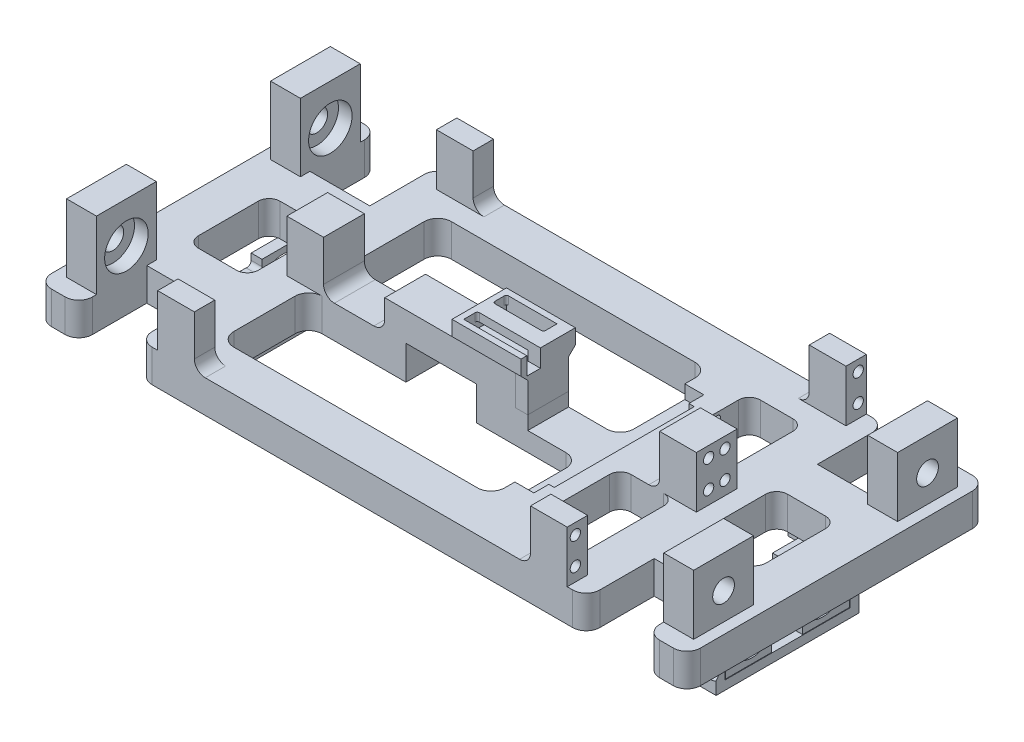
SolidWorks part; units mm, degrees
note: The reader was unsure of these and kept them because the rebuilt part matched: shared geometry of "Sketch42<4>".
other "DogBody"
other "EspHolder"
other "frontCover"
ref_plane "Front Plane" through (0, 0, 0) normal (0, 0, 1) x (1, 0, 0)
ref_plane "Top Plane" through (0, 0, 0) normal (0, 1, 0) x (1, 0, 0)
ref_plane "Right Plane" through (0, 0, 0) normal (1, 0, 0) x (0, 0, -1)
sketch "Sketch1" plane through (0, 0, 0) normal (0, 1, 0) x (1, 0, 0)
  line L0 (-104.3, -55) -> (-104.3, -7.5)
  line L1 (-119.3, -55) -> (-104.3, -55)
  line L2 (-119.3, -55) -> (-119.3, 55)
  line L3 (-119.3, 55) -> (-104.3, 55)
  line L4 (119.3, -55) -> (119.3, 55)
  line L5 (104.3, 55) -> (104.3, 7.5)
  line L6 (-82.3, -55) -> (-82.3, -7.5)
  line L7 (-67.3, -40) -> (-67.3, -7.5)
  line L8 (82.3, -55) -> (82.3, -7.5)
  line L9 (67.3, -40) -> (67.3, -7.5)
  line L10 (-119.3, 0) -> (119.3, 0) construction
  line L11 (-104.3, -7.5) -> (-82.3, -7.5)
  line L12 (-104.3, 7.5) -> (-82.3, 7.5)
  line L15 (-67.3, 40) -> (67.3, 40)
  line L16 (-82.3, 55) -> (82.3, 55)
  line L18 (104.3, 55) -> (119.3, 55)
  line L19 (104.3, -55) -> (119.3, -55)
  line L21 (-82.3, -55) -> (82.3, -55)
  line L22 (-67.3, -40) -> (67.3, -40)
  line L23 (-104.3, 7.5) -> (-104.3, 55)
  line L24 (-82.3, 7.5) -> (-82.3, 55)
  line L25 (-67.3, 7.5) -> (-67.3, 40)
  line L26 (67.3, 7.5) -> (67.3, 40)
  line L27 (82.3, 7.5) -> (82.3, 55)
  line L28 (104.3, -7.5) -> (104.3, -55)
  line L29 (-119.3, 7.5) -> (119.3, 7.5) construction
  line L30 (-119.3, -7.5) -> (119.3, -7.5) construction
  line L31 (82.3, -7.5) -> (104.3, -7.5)
  line L32 (82.3, 7.5) -> (104.3, 7.5)
  line L33 (-67.3, -7.5) -> (67.3, -7.5)
  line L34 (-67.3, 7.5) -> (67.3, 7.5)
  line L35 (-104.3, 55) -> (-82.3, 55) construction
  line L36 (82.3, 55) -> (104.3, 55) construction
  line L37 (82.3, -55) -> (104.3, -55) construction
  line L38 (-82.3, -55) -> (-104.3, -55) construction
  dimension "D1" = 55
  dimension "D2" = 110
  dimension "D3" = 15
  dimension "D4" = 22
  dimension "D5" = 15
  dimension "D6" = 15
  dimension "D7" = 22
  dimension "D8" = 15
  dimension "D11" = 80
  dimension "D12" = 40
  dimension "D13" = 238.6
  dimension "D14" = 119.3
  dimension "D9" = 7.5
  dimension "D10" = 7.5
extrude "Boss-Extrude1" add sketch "Sketch1" along normal blind 12
sketch "Sketch2" plane through (0, 12, 0) normal (0, 1, 0) x (1, 0, 0)
  line L0 (-82.3, 55) -> (-82.3, 7.5) construction
  line L1 (-75.3, 47.5) -> (-63.3, 47.5)
  line L2 (-75.3, 47.5) -> (-75.3, 55)
  line L3 (-75.3, 55) -> (-63.3, 55)
  line L4 (-63.3, 47.5) -> (-63.3, 55)
  line L5 (82.3, 55) -> (-82.3, 55) construction
  line L6 (-75.3, 52) -> (-63.3, 52) construction
  line L7 (-112.3144, 27.5) -> (114.0355, 27.5) construction
  line L8 (0, 0) -> (0, 64.2149) construction
  line L9 (-75.3, 3) -> (-63.3, 3) construction
  line L12 (-75.3, 7.5) -> (-63.3, 7.5)
  line L14 (0, 0) -> (-136.6898, 0) construction
  line L15 (-75.3, -52) -> (-63.3, -52) construction
  line L16 (-75.3, -55) -> (-63.3, -55)
  line L17 (-63.3, -47.5) -> (-63.3, -55)
  line L18 (-75.3, -47.5) -> (-63.3, -47.5)
  line L19 (-75.3, -47.5) -> (-75.3, -55)
  line L20 (-75.3, -3) -> (-63.3, -3) construction
  line L21 (-75.3, -7.5) -> (-63.3, -7.5)
  line L22 (-63.3, -7.5) -> (-63.3, 0)
  line L23 (-63.3, 0) -> (-63.3, 7.5)
  line L24 (-75.3, 7.5) -> (-75.3, 0)
  line L25 (-75.3, 0) -> (-75.3, -7.5)
  line L26 (75.3, -52) -> (63.3, -52) construction
  line L27 (75.3, -47.5) -> (75.3, -55)
  line L28 (75.3, -47.5) -> (63.3, -47.5)
  line L29 (63.3, -47.5) -> (63.3, -55)
  line L30 (75.3, -55) -> (63.3, -55)
  line L31 (75.3, -3) -> (63.3, -3) construction
  line L32 (75.3, 3) -> (63.3, 3) construction
  line L33 (75.3, 7.5) -> (75.3, 0)
  line L34 (75.3, 7.5) -> (63.3, 7.5)
  line L35 (63.3, 0) -> (63.3, 7.5)
  line L36 (63.3, -7.5) -> (63.3, 0)
  line L37 (75.3, -7.5) -> (63.3, -7.5)
  line L38 (75.3, 0) -> (75.3, -7.5)
  line L39 (75.3, 52) -> (63.3, 52) construction
  line L40 (75.3, 55) -> (63.3, 55)
  line L41 (63.3, 47.5) -> (63.3, 55)
  line L42 (75.3, 47.5) -> (63.3, 47.5)
  line L43 (75.3, 47.5) -> (75.3, 55)
  point P29 (-63.3, 0)
  point P32 (-75.3, 0)
  dimension "D1" = 7
  dimension "D2" = 7.5
  dimension "D3" = 12
  dimension "D5" = 24.5
extrude "Boss-Extrude2" add sketch "Sketch2" along normal blind 19
sketch "Sketch3" plane through (-75.3, 0, 0) normal (-1, 0, 0) x (0, 0, 1)
  line L0 (-27.5, -10.7851) -> (-27.5, 36.9377) construction
  line L1 (-47.5, 31) -> (-47.5, 12) construction
  line L2 (-55, 12) -> (55, 12) construction
  line L3 (0, 0) -> (0, 40.8102) construction
  line L4 (-55, 0) -> (55, 0) construction
  circle A0 centre (-52, 17) radius 1.9
  circle A1 centre (-52, 27) radius 1.9
  circle A2 centre (-3, 17) radius 1.9
  circle A3 centre (-3, 27) radius 1.9
  circle A4 centre (3, 27) radius 1.9
  circle A5 centre (3, 17) radius 1.9
  circle A6 centre (52, 17) radius 1.9
  circle A7 centre (52, 27) radius 1.9
  dimension "D3" = 3.8
  dimension "D4" = 3.8
  dimension "D1" = 4.5
  dimension "D2" = 4.5
  dimension "D5" = 10
  dimension "D6" = 5
  dimension "D7" = 24.5
extrude "Cut-Extrude1" cut sketch "Sketch3" against normal through all
sketch "Sketch4" plane through (104.3, 0, 0) normal (-1, 0, 0) x (0, 0, 1)
  line L0 (47.5, 31) -> (47.5, 12) construction
  line L1 (-55, 12) -> (55, 12) construction
  line L2 (-1000, 0) -> (49000, 0) construction
  line L3 (0, -1000) -> (0, 49000) construction
  line L4 (55, 31) -> (55, 12) construction
  line L5 (-48.5, 12) -> (-26.5, 12)
  line L6 (-48.5, 12) -> (-48.5, 34)
  line L7 (-48.5, 34) -> (-26.5, 34)
  line L8 (-26.5, 12) -> (-26.5, 34)
  line L9 (48.5, 12) -> (26.5, 12)
  line L10 (48.5, 12) -> (48.5, 34)
  line L11 (48.5, 34) -> (26.5, 34)
  line L12 (26.5, 12) -> (26.5, 34)
  line L13 (-55, 31) -> (-55, 12) construction
  circle A0 centre (37.5, 22) radius 8
  circle A1 centre (-37.5, 22) radius 8
  dimension "D1" = 16
  dimension "D2" = 10
  dimension "D3" = 10
  dimension "D4" = 22
  dimension "D5" = 22
  dimension "D6" = 22
  dimension "D7" = 22
  dimension "D8" = 6.5
  dimension "D9" = 6.5
extrude "Boss-Extrude3" add sketch "Sketch4" against normal blind 5 separate body
sketch "Sketch6" plane through (109.3, 0, 0) normal (1, 0, 0) x (0, 0, -1)
  line L5 (-48.5, 12) -> (-26.5, 12)
  line L10 (48.5, 12) -> (26.5, 12)
  line L11 (48.5, 12) -> (48.5, 34)
  line L12 (48.5, 34) -> (26.5, 34)
  line L13 (26.5, 12) -> (26.5, 34)
  line L14 (-48.5, 12) -> (-48.5, 34)
  line L15 (-48.5, 34) -> (-26.5, 34)
  line L16 (-26.5, 12) -> (-26.5, 34)
  circle A0 centre (-37.5, 22) radius 4
  circle A1 centre (37.5, 22) radius 4
  dimension "D1" = 8
  dimension "D2" = 8
extrude "Boss-Extrude4" add sketch "Sketch6" along normal blind 6
mirror "Mirror1" about plane through (0, 0, 0) normal (1, 0, 0) of bodies 228 106 107
sketch "Sketch7" plane through (0, 0, 0) normal (0, 1, 0) x (1, 0, 0)
  line L0 (-104.3, 26.5) -> (-104.3, 48.5) construction
  line L1 (-104.3, 30) -> (-82.3, 30)
  line L2 (-104.3, 30) -> (-104.3, 15)
  line L4 (-82.3, 30) -> (-82.3, 15)
  line L5 (-75.3, 47.5) -> (-63.3, 47.5) construction
  line L7 (-104.3, 15) -> (-82.3, 15)
  line L9 (-1000, 0) -> (49000, 0) construction
  line L10 (0, -1000) -> (0, 49000) construction
  line L11 (104.3, 30) -> (104.3, 15)
  line L12 (104.3, 15) -> (82.3, 15)
  line L13 (82.3, 30) -> (82.3, 15)
  line L14 (104.3, 30) -> (82.3, 30)
  line L15 (104.3, -30) -> (82.3, -30)
  line L16 (82.3, -30) -> (82.3, -15)
  line L17 (104.3, -15) -> (82.3, -15)
  line L18 (104.3, -30) -> (104.3, -15)
  line L19 (-104.3, -30) -> (-104.3, -15)
  line L20 (-104.3, -15) -> (-82.3, -15)
  line L21 (-82.3, -30) -> (-82.3, -15)
  line L22 (-104.3, -30) -> (-82.3, -30)
  dimension "D1" = 17.5
  dimension "D2" = 15
  dimension "D3" = 22
extrude "Boss-Extrude5" add sketch "Sketch7" along normal blind 12
sketch "Sketch8" plane through (0, 12, 0) normal (0, 1, 0) x (1, 0, 0)
  line L1 (-104.3, 15) -> (-82.3, 15)
  line L2 (-104.3, 15) -> (-104.3, -15)
  line L3 (-104.3, -15) -> (-82.3, -15)
  line L4 (-82.3, 15) -> (-82.3, -15)
  line L5 (82.3, -15) -> (104.3, -15)
  line L6 (82.3, -15) -> (82.3, 15)
  line L7 (82.3, 15) -> (104.3, 15)
  line L8 (104.3, -15) -> (104.3, 15)
extrude "Cut-Extrude2" cut sketch "Sketch8" against normal through all
sketch "Sketch14" plane through (0, 0, 0) normal (0, 1, 0) x (1, 0, 0)
  line L0 (-67.3, -40) -> (67.3, -40) construction
  line L1 (-7.5, -40) -> (7.5, -40)
  line L2 (-7.5, -40) -> (-7.5, -7.5)
  line L3 (-7.5, 40) -> (7.5, 40)
  line L4 (7.5, -40) -> (7.5, -7.5)
  line L5 (67.3, 40) -> (-67.3, 40) construction
  line L6 (63.3, -7.5) -> (-63.3, -7.5) construction
  line L7 (-63.3, 7.5) -> (63.3, 7.5) construction
  line L8 (7.5, -7.5) -> (-7.5, -7.5)
  line L9 (-7.5, 7.5) -> (7.5, 7.5)
  line L10 (7.5, 7.5) -> (7.5, 40)
  line L11 (-7.5, 7.5) -> (-7.5, 40)
  dimension "D1" = 15
  dimension "D2" = 7.5
extrude "Boss-Extrude8" add sketch "Sketch14" along normal up to surface (12 mm away) up to face at (0, 12, 0)
sketch "Sketch15" plane through (0, 12, 0) normal (0, 1, 0) x (1, 0, 0)
  line L1 (13.3, -31.25) -> (39.3, -31.25)
  line L2 (13.3, -31.25) -> (13.3, 31.25)
  line L4 (39.3, -31.25) -> (39.3, 31.25)
  line L5 (75.3, 47.5) -> (75.3, 55) construction
  line L8 (13.3, 31.25) -> (39.3, 31.25)
  line L9 (-47.3, 14) -> (0.7, 14)
  line L10 (-47.3, 14) -> (-47.3, -14)
  line L11 (-47.3, -14) -> (0.7, -14)
  line L12 (0.7, 14) -> (0.7, -14)
  line L13 (13.3, 27.75) -> (39.3, 27.75) construction
  line L14 (13.3, -27.75) -> (39.3, -27.75) construction
  line L15 (-75.3, 55) -> (-75.3, 47.5) construction
  line L16 (-39.3, -998.765) -> (-39.3, 49001.235) construction
  line L17 (39.3, -1009.0627) -> (39.3, 48990.9373) construction
  point P17 (-75.3, 51.25)
  dimension "D1" = 26
  dimension "D2" = 36
  dimension "D3" = 48
  dimension "D4" = 28
  dimension "D5" = 31.25
  dimension "D6" = 62.5
  dimension "D7" = 55.5
  dimension "D8" = 3.5
  dimension "D9" = 28
  dimension "D10" = 14
  dimension "D11" = 12.6
sketch "Sketch16" plane through (0, 12, 0) normal (0, 1, 0) x (1, 0, 0)
  line L1 (-7.5, 40) -> (7.5, 40)
  line L2 (-7.5, 40) -> (-7.5, 7.5)
  line L3 (-7.5, 7.5) -> (7.5, 7.5)
  line L4 (7.5, 40) -> (7.5, 7.5)
  line L5 (-7.5, -7.5) -> (7.5, -7.5)
  line L6 (-7.5, -7.5) -> (-7.5, -40)
  line L7 (-7.5, -40) -> (7.5, -40)
  line L8 (7.5, -7.5) -> (7.5, -40)
extrude "Cut-Extrude8" cut sketch "Sketch16" against normal through all
sketch "Sketch17" plane through (0, 0, 0) normal (0, 1, 0) x (1, 0, 0)
  line L0 (67.3, 40) -> (-67.3, 40) construction
  line L1 (32.3, 40) -> (47.3, 40)
  line L2 (32.3, 40) -> (32.3, 7.5)
  line L3 (32.3, 7.5) -> (47.3, 7.5)
  line L4 (47.3, 40) -> (47.3, 7.5)
  line L5 (-63.3, 7.5) -> (63.3, 7.5) construction
  line L6 (63.3, -7.5) -> (-63.3, -7.5) construction
  line L7 (32.3, -7.5) -> (47.3, -7.5)
  line L8 (32.3, -7.5) -> (32.3, -40)
  line L9 (32.3, -40) -> (47.3, -40)
  line L10 (47.3, -7.5) -> (47.3, -40)
  line L11 (-67.3, -40) -> (67.3, -40) construction
  line L12 (39.3, -201009.0627) -> (39.3, 248990.9373) construction
  dimension "D1" = 15
  dimension "D2" = 15
  dimension "D3" = 7
  dimension "D4" = 7
extrude "Boss-Extrude9" add sketch "Sketch17" along normal up to surface (12 mm away) up to face at (-93.3, 12, 0)
extrude "Cut-Extrude9" cut sketch "Sketch15" against normal blind 5 contours L8 L2 L1 L4
sketch "Sketch18" plane through (39.3, 0, 0) normal (-1, 0, 0) x (0, 0, 1)
  line L0 (31.25, 7) -> (-31.25, 7) construction
  line L1 (-31.25, 12) -> (-31.25, 7) construction
  line L2 (31.25, 12) -> (31.25, 7) construction
  circle A0 centre (28.25, 9.7) radius 1.2
  circle A1 centre (-28.25, 9.7) radius 1.2
  dimension "D1" = 2.4
  dimension "D2" = 2.4
  dimension "D3" = 2.7
  dimension "D4" = 2.7
  dimension "D5" = 3
  dimension "D6" = 3
extrude "Cut-Extrude10" cut sketch "Sketch18" against normal up to next
sketch "Sketch19" plane through (39.3, 0, 0) normal (-1, 0, 0) x (0, 0, 1)
  line L0 (-31.25, 7) -> (-7.5, 7) construction
  line L1 (-25.75, 7) -> (25.75, 7)
  line L2 (-25.75, 7) -> (-25.75, 14)
  line L3 (-25.75, 14) -> (25.75, 14)
  line L4 (25.75, 7) -> (25.75, 14)
  dimension "D1" = 7
  dimension "D2" = 51.5
  dimension "D3" = 25.75
extrude "Cut-Extrude11" cut sketch "Sketch19" against normal blind 2
sketch "Sketch21" plane through (0, 0, 7.5) normal (0, 0, 1) x (1, 0, 0)
  line L0 (-47.3, 12) -> (0.7, 12) construction
  line L1 (-39.3, 12) -> (2.3491, 12)
  line L2 (-39.3, 12) -> (-39.3, 23)
  line L3 (-39.3, 23) -> (8.7, 23)
  line L5 (13.3, 12) -> (-63.3, 12) construction
  line L7 (8.7, 23) -> (8.7, 12)
  line L8 (2.3491, 12) -> (8.7, 12)
  dimension "D2" = 11
  dimension "D3" = 48
extrude "Boss-Extrude10" add sketch "Sketch21" against normal up to surface (15 mm away) up to face at (63.3, 13.75, -7.5)
sketch "Sketch22" plane through (0, 0, 7.5) normal (0, 0, 1) x (1, 0, 0)
  line L0 (8.7, 12) -> (13.3, 12)
  line L1 (13.3, 12) -> (13.3, 23)
  line L3 (8.7, 23) -> (13.3, 23)
  line L5 (8.7, 23) -> (8.7, 12)
extrude "Boss-Extrude11" add sketch "Sketch22" against normal up to surface (15 mm away) separate body up to face at (63.3, 13.75, -7.5)
sketch "Sketch25" plane through (13.3, 0, 0) normal (1, 0, 0) x (0, 0, -1)
  line L0 (-7.5, 23) -> (7.5, 23)
  line L2 (-7.5, 31) -> (7.5, 31) construction
  line L3 (10, 31) -> (-10, 31)
  line L6 (10, 31) -> (10, 25.5)
  line L7 (7.5, 23) -> (10, 25.5)
  line L8 (-10, 25.5) -> (-10, 31)
  line L9 (-7.5, 23) -> (-10, 25.5)
  dimension "D1" = 20
  dimension "D2" = 10
  dimension "D3" = 5.5
  dimension "D4" = 5.5
extrude "Boss-Extrude12" add sketch "Sketch25" against normal blind 4.6
sketch "Sketch28" plane through (8.7, 0, 0) normal (-1, 0, 0) x (0, 0, 1)
  line L0 (-10, 31) -> (10, 31)
  line L1 (10, 31) -> (10, 25.5)
  line L2 (10, 31) -> (10, 25.5) construction
  line L3 (10, 25.5) -> (7.85, 25.5)
  line L4 (7.85, 25.5) -> (7.85, 28)
  line L5 (7.85, 28) -> (-7.85, 28)
  line L6 (-7.85, 28) -> (-7.85, 25.5)
  line L7 (-7.85, 25.5) -> (-10, 25.5)
  line L8 (-10, 25.5) -> (-10, 31) construction
  line L9 (-10, 25.5) -> (-10, 31)
  dimension "D1" = 15.7
  dimension "D2" = 7.85
  dimension "D3" = 3
  dimension "D4" = 2.5
  dimension "D5" = 2.5
extrude "Boss-Extrude13" add sketch "Sketch28" along normal blind 18.6
sketch "Sketch29" plane through (-9.9, 0, 0) normal (-1, 0, 0) x (0, 0, 1)
  line L1 (-10, 31) -> (10, 31)
  line L2 (-10, 31) -> (-10, 25.5)
  line L3 (-10, 25.5) -> (10, 25.5)
  line L4 (10, 31) -> (10, 25.5)
extrude "Boss-Extrude14" add sketch "Sketch29" along normal blind 2.15
sketch "Sketch31" plane through (0, 28, 0) normal (0, -1, 0) x (1, 0, 0)
  line L0 (13.3, 31.25) -> (13.3, -31.25) construction
  line L1 (7.9, 7.85) -> (4.5, 7.85)
  line L2 (8.7, 7.05) -> (8.7, 3.65) construction
  line L3 (7.9, 2.85) -> (4.5, 2.85)
  line L5 (7.9, 7.85) -> (13.3, 7.85)
  line L6 (7.9, 7.85) -> (7.9, 2.85)
  line L7 (7.9, 2.85) -> (13.3, 2.85)
  line L20 (13.3, 7.85) -> (13.3, 2.85)
  line L21 (7.9, 2.85) -> (13.3, 2.85)
  line L22 (-9.9, -3.65) -> (-9.9, -7.05)
  line L23 (-5.7, -2.85) -> (-9.1, -2.85)
  line L24 (-5.7, -7.85) -> (-9.1, -7.85)
  line L30 (-12.05, 10) -> (-12.05, -10) construction
  line L31 (7.9, -2.85) -> (4.5, -2.85)
  line L32 (-12.05, -10) -> (13.3, -10) construction
  line L33 (8.7, -3.65) -> (8.7, -7.05)
  line L35 (7.9, -7.85) -> (4.5, -7.85)
  line L37 (-5.4657, 7.85) -> (-8.8657, 7.85)
  line L38 (-9.9, 7.05) -> (-9.9, 3.65)
  line L39 (-5.7, 2.85) -> (-9.1, 2.85)
  line L40 (4.5, 7.85) -> (-5.4657, 7.85)
  line L41 (4.5, 2.85) -> (-5.7, 2.85)
  line L42 (4.5, -2.85) -> (-5.7, -2.85)
  line L43 (4.5, -7.85) -> (-5.7, -7.85)
  arc A4 (8.7, 3.65) -> (7.9, 2.85) centre (7.9, 3.65) cw construction
  arc A5 (7.9, 7.85) -> (8.7, 7.05) centre (7.9, 7.05) cw construction
  arc A19 (-9.1, -7.85) -> (-9.9, -7.05) centre (-9.1, -7.05) cw
  arc A21 (-9.1, -2.85) -> (-9.9, -3.65) centre (-9.1, -3.65) ccw
  arc A28 (7.9, -2.85) -> (8.7, -3.65) centre (7.9, -3.65) cw
  arc A29 (7.9, -7.85) -> (8.7, -7.05) centre (7.9, -7.05) ccw
  arc A32 (-8.8657, 7.85) -> (-9.9, 7.05) centre (-9.1008, 7.0853) ccw
  arc A34 (-9.1, 2.85) -> (-9.9, 3.65) centre (-9.1, 3.65) cw
  point P21 (3.7, 2.85)
  point P26 (8.7, 7.85)
  point P29 (3.7, 7.85)
  dimension "D15" = 0.8
  dimension "D16" = 0.8
  dimension "D1" = 5
  dimension "D2" = 5
  dimension "D7" = 2.15
  dimension "D9" = 2.15
  dimension "D11" = 5
  dimension "D13" = 0.8
  dimension "D14" = 3.4
  dimension "D19" = 3.4
  dimension "D20" = 0.8
  dimension "D21" = 3.4
  dimension "D23" = 0.8
extrude "Cut-Extrude12" cut sketch "Sketch31" against normal through all
sketch "Sketch41" plane through (0, 0, 0) normal (0, -1, 0) x (1, 0, 0)
  line L0 (88.3, 21) -> (98.3, 21) construction
  line L1 (88.3, -22.75) -> (98.3, -22.75) construction
  line L2 (88.3, -22.75) -> (88.3, 22.75) construction
  line L3 (88.3, 22.75) -> (98.3, 22.75) construction
  line L4 (98.3, -22.75) -> (98.3, 22.75) construction
  line L5 (88.3, -21) -> (98.3, -21) construction
  line L6 (104.3, -15) -> (104.3, 15) construction
  line L8 (93.3, 22.75) -> (93.3, -22.75) construction
  line L24 (93.3, -22.75) -> (90.3, -22.75)
  line L25 (93.3, -22.75) -> (93.3, 22.75)
  line L26 (93.3, 22.75) -> (90.3, 22.75)
  line L27 (90.3, -22.75) -> (90.3, 22.75)
  line L28 (90.3, 22.75) -> (93.3, 22.75)
  line L29 (90.3, 22.75) -> (90.3, 26.25)
  line L30 (90.3, 26.25) -> (93.3, 26.25)
  line L31 (93.3, 22.75) -> (93.3, 26.25)
  line L32 (90.3, -22.75) -> (93.3, -22.75)
  line L33 (90.3, -22.75) -> (90.3, -26.25)
  line L34 (90.3, -26.25) -> (93.3, -26.25)
  line L35 (93.3, -22.75) -> (93.3, -26.25)
  line M29 (82.3, 15) -> (104.3, 15)
  line M31 (104.3, -15) -> (82.3, -15)
  dimension "D1" = 45.5
  dimension "D2" = 22.75
  dimension "D3" = 42
  dimension "D4" = 21
  dimension "D5" = 10
  dimension "D6" = 6
  dimension "D7" = 3.5
  dimension "D8" = 3.5
  dimension "D9" = 3
extrude "Boss-Extrude18" add sketch "Sketch41" along normal blind 24 separate body contours L26 L31 L30 L29 | L27 L25 L26 M29 | L27 L25 M31 M29 | L27 L24 L25 M31 | L35 L24 L33 L34
sketch "Sketch42" plane through (93.3, 0, 0) normal (1, 0, 0) x (0, 0, -1)
  line L1 (-26.25, 0) -> (26.25, 0)
  line L2 (-26.25, 0) -> (-26.25, -24)
  line L3 (-26.25, -24) -> (26.25, -24)
  line L4 (26.25, 0) -> (26.25, -24)
  line L5 (-22.95, 0) -> (22.95, 0)
  line L6 (-22.95, 0) -> (-22.95, -20.7)
  line L7 (-22.95, -20.7) -> (22.95, -20.7)
  line L8 (22.95, 0) -> (22.95, -20.7)
  line L9 (-5.5, -5.0608) -> (5.5, -5.0608) construction
  line L10 (-5.5, -5.0608) -> (-5.5, 3.3558) construction
  line L11 (-5.5, 3.3558) -> (5.5, 3.3558) construction
  line L12 (5.5, -5.0608) -> (5.5, 3.3558) construction
  line L13 (-5.5, -3.3) -> (-19.95, -3.3)
  line L14 (-5.5, -3.3) -> (-5.5, 0)
  line L15 (-5.5, 0) -> (-19.95, 0)
  line L16 (-19.95, -3.3) -> (-19.95, 0)
  line L17 (5.5, -3.3) -> (19.95, -3.3)
  line L18 (5.5, -3.3) -> (5.5, 0)
  line L19 (5.5, 0) -> (19.95, 0)
  line L20 (19.95, -3.3) -> (19.95, 0)
  line L21 (5.5, -3.5) -> (-5.5, -3.5)
  line L22 (5.5, -3.5) -> (5.5, 0)
  line L23 (5.5, 0) -> (-5.5, 0)
  line L24 (-5.5, -3.5) -> (-5.5, 0)
  line M8 (26.25, 0) -> (-26.25, 0)
  line M9 (-26.25, 0) -> (-26.25, -24)
  line M10 (-26.25, -24) -> (26.25, -24)
  line M11 (26.25, -24) -> (26.25, 0)
  dimension "D1" = 3.3
  dimension "D2" = 3.3
  dimension "D3" = 3.3
  dimension "D4" = 11
  dimension "D5" = 5.5
  dimension "D6" = 3.3
  dimension "D7" = 3.3
  dimension "D8" = 3
  dimension "D9" = 3
  dimension "D10" = 3.5
extrude "Boss-Extrude19" add sketch "Sketch42" along normal blind 8 contours L8 L7 L6 M8 M9 M10 M11
sketch "Sketch43" plane through (93.3, 0, 0) normal (1, 0, 0) x (0, 0, -1)
  line L0 (-55, 0) -> (55, 0) construction
  line L1 (-21.25, -1.5) -> (21.25, -1.5) construction
  line L2 (-21.25, -1.5) -> (-21.25, -19) construction
  line L3 (-21.25, -19) -> (21.25, -19) construction
  line L4 (21.25, -1.5) -> (21.25, -19) construction
  line L5 (-22.95, 0) -> (-22.95, -20.7) construction
  line L7 (22.95, 0) -> (22.95, -20.7) construction
  line L9 (-22.95, -20.7) -> (22.95, -20.7) construction
  circle A1 centre (-21.25, -1.5) radius 0.9
  circle A2 centre (-21.25, -19) radius 0.9
  circle A3 centre (21.25, -1.5) radius 0.9
  circle A4 centre (21.25, -19) radius 0.9
  dimension "D5" = 1.8
  dimension "D6" = 1.8
  dimension "D7" = 1.8
  dimension "D8" = 1.8
  dimension "D1" = 1.5
  dimension "D2" = 1.7
  dimension "D3" = 1.7
  dimension "D4" = 1.7
sketch "Sketch44" plane through (90.3, 0, 0) normal (-1, 0, 0) x (0, 0, 1)
  line L0 (-26.25, 0) -> (26.25, 0) construction
  line L1 (-26.25, 0) -> (-18.75, 0)
  line L2 (-26.25, 0) -> (-26.25, -5)
  line L3 (-26.25, -5) -> (-18.75, -5)
  line L4 (-18.75, 0) -> (-18.75, -5)
  line L6 (26.25, 0) -> (18.75, 0)
  line L7 (26.25, 0) -> (26.25, -5)
  line L8 (26.25, -5) -> (18.75, -5)
  line L9 (18.75, 0) -> (18.75, -5)
  dimension "D1" = 7.5
  dimension "D2" = 7.5
  dimension "D3" = 5
  dimension "D4" = 5
  dimension "D5" = 18.75
  dimension "D6" = 18.75
extrude "Boss-Extrude20" add sketch "Sketch44" along normal blind 7.5
sketch "Sketch45" plane through (0, -5, 0) normal (0, -1, 0) x (1, 0, 0)
  line L0 (82.8, -26.25) -> (82.8, -18.75) construction
  line L1 (82.8, -26.25) -> (90.3, -26.25) construction
  line L2 (82.8, 18.75) -> (82.8, 26.25) construction
  line L3 (82.8, 26.25) -> (90.3, 26.25) construction
  circle A0 centre (86.55, 22.5) radius 2.75
  circle A1 centre (86.55, -22.5) radius 2.75
  dimension "D3" = 5.5
  dimension "D4" = 5.5
  dimension "D1" = 3.75
  dimension "D2" = 3.75
  dimension "D5" = 3.75
  dimension "D6" = 3.75
extrude "Cut-Extrude20" cut sketch "Sketch45" against normal blind 3
sketch "Sketch47" plane through (0, -2, 0) normal (0, -1, 0) x (1, 0, 0)
  circle A3 centre (86.55, -22.5) radius 1.4
  circle A4 centre (86.55, 22.5) radius 1.4
  dimension "D1" = 2.8
  dimension "D2" = 2.8
extrude "Cut-Extrude22" cut sketch "Sketch47" against normal blind 10
sketch "Sketch48" plane through (93.3, 0, 0) normal (1, 0, 0) x (0, 0, -1)
  line L0 (-13, -10.5) -> (13, -10.5) construction
  line L1 (-5, -2.5) -> (-5, -0.2)
  line L2 (-22.95, -20.7) -> (22.95, -20.7) construction
  line L3 (-5.95, -17.7) -> (-5.95, -20.5)
  line L4 (-3.75, -17.7) -> (3.35, -17.7) construction
  line L5 (-3.75, -15.5) -> (3.35, -15.5)
  line L7 (5.55, -17.7) -> (5.55, -20.5)
  line L8 (-22.95, -20.7) -> (22.95, -20.7) construction
  line L9 (-3.5, -2.5) -> (3.8789, -2.5486) construction
  line L11 (-3.5, -4) -> (3.5, -4)
  line L12 (-55, 0) -> (55, 0) construction
  line L13 (-22.95, 0) -> (-22.95, -20.7) construction
  line L14 (-22.75, -20.5) -> (-5.95, -20.5)
  line L15 (-22.75, -20.5) -> (-22.75, -0.2)
  line L16 (-22.75, -0.2) -> (-5, -0.2)
  line L17 (22.75, -20.5) -> (22.75, -0.2)
  line L18 (22.95, 0) -> (22.95, -20.7) construction
  line L19 (5.55, -20.5) -> (22.75, -20.5)
  line L20 (5.3789, -2.5486) -> (5.3789, -0.2)
  line L21 (5.3789, -0.2) -> (22.75, -0.2)
  circle A0 centre (-13, -10.5) radius 8.1
  circle A1 centre (13, -10.5) radius 8.1
  arc A2 (-3.75, -15.5) -> (-5.95, -17.7) centre (-3.75, -17.7) ccw
  arc A3 (5.55, -17.7) -> (3.35, -15.5) centre (3.35, -17.7) ccw
  arc A5 (-5, -2.5) -> (-3.5, -4) centre (-3.5, -2.5) ccw
  arc A6 (3.5, -4) -> (5.3789, -2.5486) centre (3.8789, -2.5486) ccw
  point P13 (0, -17.7)
  point P23 (0, -2.5)
  point P29 (-4.5607, -3.5607)
  dimension "D1" = 16.2
  dimension "D2" = 16.2
  dimension "D6" = 2.2
  dimension "D7" = 11.5
  dimension "D10" = 1.5
  dimension "D12" = 5
  dimension "D8" = 2.2
  dimension "D3" = 26
  dimension "D4" = 13
  dimension "D5" = 10.2
  dimension "D11" = 10
  dimension "D14" = 0.2
  dimension "D15" = 0.2
  dimension "D16" = 0.2
  dimension "D17" = 0.2
extrude "Boss-Extrude22" add sketch "Sketch48" along normal blind 4 from offset 5 separate body
sketch "Sketch50" plane through (0, 0, 0) normal (0, -1, 0) x (1, 0, 0)
  line L0 (-29, -5.5) -> (-8, -5.5) construction
  line L1 (-31.5, -8) -> (-5.5, -8)
  line L2 (-31.5, -8) -> (-31.5, 8)
  line L3 (-31.5, 8) -> (-5.5, 8)
  line L4 (-5.5, -8) -> (-5.5, 8)
  line L6 (-31.5, 8) -> (-5.5, 8) construction
  line L7 (-31.5, 8) -> (-31.5, 5.3) construction
  line L8 (-31.5, 5.3) -> (-5.5, 5.3)
  line L9 (-5.5, 8) -> (-5.5, 5.3) construction
  circle A0 centre (-29, -5.5) radius 1.5 construction
  circle A1 centre (-8, -5.5) radius 1.5 construction
  line M16 (32.3, 7.5) -> (-67.3, 7.5)
  line M22 (-67.3, -7.5) -> (32.3, -7.5)
  dimension "D4" = 3
  dimension "D5" = 3
  dimension "D1" = 16
  dimension "D2" = 26
  dimension "D3" = 8
  dimension "D6" = 2.5
  dimension "D7" = 2.5
  dimension "D8" = 2.5
  dimension "D9" = 2.7
  dimension "D10" = 5.5
extrude "Cut-Extrude23" cut sketch "Sketch50" against normal blind 11 contours L2 L8 L4 M16 | L8 L2 L4 M22
sketch "Sketch53" plane through (0, 11, 0) normal (0, -1, 0) x (1, 0, 0)
  line L0 (-31.5, -7.5) -> (-31.5, 7.5) construction
  line L1 (-31.5, -7.5) -> (-5.5, -7.5) construction
  line L2 (-5.5, -7.5) -> (-5.5, 7.5) construction
  circle A0 centre (-29, -5) radius 1.4
  circle A1 centre (-8, -5) radius 1.4
  dimension "D5" = 2.8
  dimension "D6" = 2.8
  dimension "D1" = 2.5
  dimension "D2" = 2.5
  dimension "D3" = 2.5
  dimension "D4" = 2.5
  dimension "D7" = 21
extrude "Cut-Extrude26" cut sketch "Sketch53" against normal blind 8.6
sketch "Sketch54" plane through (0, 12, 0) normal (0, 1, 0) x (1, 0, 0)
  line L0 (119.3, -55) -> (119.3, 55) construction
  line L1 (104.3, 48.5) -> (119.3, 48.5)
  line L2 (104.3, 48.5) -> (104.3, 50.5)
  line L3 (104.3, 50.5) -> (119.3, 50.5)
  line L4 (119.3, 48.5) -> (119.3, 50.5)
  line L10 (119.3, -55) -> (119.3, 55) construction
  line L11 (104.3, -48.5) -> (119.3, -48.5)
  line L12 (104.3, -48.5) -> (104.3, -50.5)
  line L13 (104.3, -50.5) -> (119.3, -50.5)
  line L14 (119.3, -48.5) -> (119.3, -50.5)
  dimension "D1" = 2
  dimension "D2" = 2
sketch "Sketch55" plane through (0, 12, 0) normal (0, 1, 0) x (1, 0, 0)
  line L0 (63.3, 55) -> (-63.3, 55) construction
  line L1 (-63.3, 47.5) -> (-61.8, 47.5)
  line L2 (-63.3, 47.5) -> (-63.3, 55)
  line L3 (-63.3, 55) -> (-61.8, 55)
  line L4 (-61.8, 47.5) -> (-61.8, 55)
  line L6 (63.3, 47.5) -> (61.8, 47.5)
  line L7 (63.3, 47.5) -> (63.3, 55)
  line L8 (63.3, 55) -> (61.8, 55)
  line L9 (61.8, 47.5) -> (61.8, 55)
  line L14 (47.3, 7.5) -> (63.3, 7.5) construction
  line L15 (63.3, -7.5) -> (61.8, -7.5)
  line L16 (63.3, -7.5) -> (63.3, 7.5)
  line L17 (63.3, 7.5) -> (61.8, 7.5)
  line L18 (61.8, -7.5) -> (61.8, 7.5)
  line L19 (-63.3, -55) -> (63.3, -55) construction
  line L20 (63.3, -47.5) -> (61.8, -47.5)
  line L21 (63.3, -47.5) -> (63.3, -55)
  line L22 (63.3, -55) -> (61.8, -55)
  line L23 (61.8, -47.5) -> (61.8, -55)
  line L24 (-63.3, 7.5) -> (-39.3, 7.5) construction
  line L25 (-63.3, -47.5) -> (-61.8, -47.5)
  line L26 (-63.3, -47.5) -> (-63.3, -55)
  line L27 (-63.3, -55) -> (-61.8, -55)
  line L28 (-61.8, -47.5) -> (-61.8, -55)
  line L29 (-63.3, -7.5) -> (-61.8, -7.5)
  line L30 (-63.3, -7.5) -> (-63.3, 7.5)
  line L31 (-63.3, 7.5) -> (-61.8, 7.5)
  line L32 (-61.8, -7.5) -> (-61.8, 7.5)
  dimension "D1" = 1.5
  dimension "D2" = 1.5
  dimension "D3" = 1.5
  dimension "D4" = 1.5
  dimension "D5" = 1.5
  dimension "D6" = 1.5
extrude "Boss-Extrude27" add sketch "Sketch55" along normal up to surface (19 mm away) up to face at (-69.3, 31, 0)
extrude "Cut-Extrude27" cut sketch "Sketch42<4>" against normal up to next (3 mm away) contours L24 L21 L22 L18 L5 L14
sketch "Sketch42<4>" plane through (93.3, 0, 0) normal (1, 0, 0) x (0, 0, -1) same geometry as "Sketch42"
move or copy body "Body-Move/Copy1" bodies to move or copy 172 copy no translate (-1, 0, 0) parameters "D1"=1, "D2"=0, "D3"=0
sketch "Sketch56" plane through (0, 0, 26.25) normal (0, 0, 1) x (1, 0, 0)
  line L4 (97.3, -0.2) -> (97.3, -20.5)
  line L5 (97.3, -20.5) -> (101.3, -20.5)
  line L6 (101.3, -20.5) -> (101.3, -0.2)
  line L7 (101.3, -0.2) -> (97.3, -0.2)
  line L8 (97.3, -0.2) -> (97.3, -20.5)
  line L9 (97.3, -20.5) -> (101.3, -20.5)
  line L10 (101.3, -20.5) -> (101.3, -0.2)
  line L11 (101.3, -0.2) -> (97.3, -0.2)
  circle A0 centre (99.3, -16.5) radius 1.45
  dimension "D2" = 2.9
  dimension "D3" = 2
  dimension "D4" = 4
  dimension "D1" = 0
extrude "Cut-Extrude28" cut sketch "Sketch56" against normal blind 5 contours A0
sketch "Sketch57" plane through (0, 0, -26.25) normal (0, 0, -1) x (-1, 0, 0)
  line L4 (-97.3, -20.5) -> (-97.3, -0.2)
  line L5 (-97.3, -0.2) -> (-101.3, -0.2)
  line L6 (-101.3, -0.2) -> (-101.3, -20.5)
  line L7 (-101.3, -20.5) -> (-97.3, -20.5)
  line L8 (-97.3, -20.5) -> (-97.3, -0.2)
  line L9 (-97.3, -0.2) -> (-101.3, -0.2)
  line L10 (-101.3, -0.2) -> (-101.3, -20.5)
  line L11 (-101.3, -20.5) -> (-97.3, -20.5)
  circle A0 centre (-99.3, -4.2) radius 1.45
  dimension "D2" = 2.9
  dimension "D3" = 2
  dimension "D4" = 4
  dimension "D1" = 0
extrude "Cut-Extrude29" cut sketch "Sketch57" against normal blind 5 contours A0
chamfer "Chamfer1" distance 2 angle 45 2 edges at (97.85, -4.2, -26.25) (100.75, -16.5, 26.25)
mirror "Mirror6" about plane through (0, 0, 0) normal (1, 0, 0) of bodies 212 213
sketch "Sketch58" plane through (0, -2, 0) normal (0, -1, 0) x (1, 0, 0)
  circle A0 centre (-86.55, 22.5) radius 1.4
  circle A1 centre (-86.55, -22.5) radius 1.4
extrude "Cut-Extrude30" cut sketch "Sketch58" against normal blind 10
sketch "Sketch59" plane through (0, 11, 0) normal (0, -1, 0) x (1, 0, 0)
  line L1 (-31.5, 5.3) -> (-5.5, 5.3)
  line L2 (-31.5, 5.3) -> (-31.5, 7.5)
  line L3 (-31.5, 7.5) -> (-5.5, 7.5)
  line L4 (-5.5, 5.3) -> (-5.5, 7.5)
extrude "Cut-Extrude31" cut sketch "Sketch59" against normal blind 1.4
sketch "Sketch60" plane through (0, 34, 0) normal (0, 1, 0) x (1, 0, 0)
  line L0 (-104.3, 26.5) -> (-104.3, 48.5) construction
  line L1 (-104.3, 48.5) -> (-115.3, 48.5) construction
  line L2 (-115.3, 48.5) -> (-115.3, 26.5) construction
  line L3 (-115.3, 26.5) -> (-104.3, 26.5) construction
  line L4 (-104.3, -48.5) -> (-104.3, -26.5) construction
  line L5 (-104.3, -26.5) -> (-115.3, -26.5) construction
  line L7 (-115.3, -48.5) -> (-104.3, -48.5) construction
  line L8 (-104.3, 26.5) -> (-104.3, 48.5)
  line L9 (-104.3, 48.5) -> (-115.3, 48.5)
  line L10 (-115.3, 48.5) -> (-115.3, 26.5)
  line L11 (-115.3, 26.5) -> (-104.3, 26.5)
  line L12 (-104.3, -48.5) -> (-104.3, -26.5)
  line L13 (-104.3, -26.5) -> (-115.3, -26.5)
  line L14 (-115.3, -26.5) -> (-115.3, -48.5)
  line L15 (-115.3, -48.5) -> (-104.3, -48.5)
extrude "Boss-Extrude28" add sketch "Sketch60" along normal blind 3
sketch "Sketch62" plane through (0, 0, 0) normal (0, -1, 0) x (1, 0, 0)
  line L0 (0, -1000) -> (0, 49000) construction
  line L2 (-67.3, 7.5) -> (-67.3, 40) construction
  line L4 (-67.3, -40) -> (-67.3, -7.5) construction
  line L6 (82.3, -55) -> (-82.3, -55) construction
  line L7 (-82.3, 55) -> (82.3, 55) construction
  line L8 (32.3, -40) -> (-67.3, -40) construction
  circle A0 centre (-74.8, 25) radius 1.825
  circle A1 centre (-74.8, -25) radius 1.825
  circle A2 centre (-74.8, -47.5) radius 1.825
  circle A3 centre (-74.8, 47.5) radius 1.825
  circle A4 centre (0, 47.5) radius 1.825
  circle A5 centre (0, -47.5) radius 1.825
  circle A6 centre (74.8, -47.5) radius 1.825
  circle A7 centre (74.8, -25) radius 1.825
  circle A8 centre (74.8, 25) radius 1.825
  circle A9 centre (74.8, 47.5) radius 1.825
  dimension "D3" = 3.65
  dimension "D4" = 3.65
  dimension "D9" = 3.65
  dimension "D10" = 3.65
  dimension "D12" = 7.5
  dimension "D14" = 3.65
  dimension "D15" = 3.65
  dimension "D1" = 25
  dimension "D2" = 25
  dimension "D5" = 7.5
  dimension "D6" = 7.5
  dimension "D7" = 7.5
  dimension "D8" = 7.5
  dimension "D11" = 7.5
  dimension "D13" = 7.5
  dimension "D16" = 7.5
extrude "Cut-Extrude33" cut sketch "Sketch62" against normal blind 9
fillet "Fillet2" radius 4 22 edges at (-104.3, 6, -15) (-82.3, 6, -15) (82.3, 6, -15) (104.3, 6, -15) (104.3, 6, 15) (82.3, 6, 15) (-82.3, 6, 15) (-104.3, 6, 15) (47.3, 6, -40) (47.3, 6, -7.5) (47.3, 6, 7.5) (47.3, 6, 40) (67.3, 6, -7.5) (67.3, 6, -40) (-39.3, 12, 0) (-61.8, 12, -51.25) (61.8, 12, -51.25) (67.3, 6, 7.5) (61.8, 12, 0) (61.8, 12, 51.25) (-61.8, 12, 51.25) (-61.8, 12, 0)
fillet "Fillet4" radius 5 20 edges at (-119.3, 6, -55) (-104.3, 6, -55) (-82.3, 6, -55) (-119.3, 6, 55) (-104.3, 6, 55) (-82.3, 6, 55) (119.3, 6, -55) (104.3, 6, -55) (82.3, 6, -55) (119.3, 6, 55) (104.3, 6, 55) (82.3, 6, 55) (32.3, 3.5, -7.5) (-67.3, 6, -7.5) (-67.3, 6, 40) (32.3, 6, 40) (32.3, 3.5, 7.5) (-67.3, 6, 7.5) (-67.3, 6, -40) (32.3, 6, -40)
sketch "Sketch64" plane through (0, 28, 0) normal (0, 1, 0) x (1, 0, 0)
  line L4 (8.7, -2.85) -> (8.7, -7.85)
  line L5 (8.7, -7.85) -> (13.3, -7.85)
  line L6 (13.3, -7.85) -> (13.3, -2.85)
  line L7 (13.3, -2.85) -> (8.7, -2.85)
  line L8 (8.7, -2.85) -> (8.7, -7.85)
  line L9 (8.7, -7.85) -> (13.3, -7.85)
  line L10 (13.3, -7.85) -> (13.3, -2.85)
  line L11 (13.3, -2.85) -> (8.7, -2.85)
  dimension "D1" = 0
extrude "Cut-Extrude34" cut sketch "Sketch64" against normal blind 3.5
